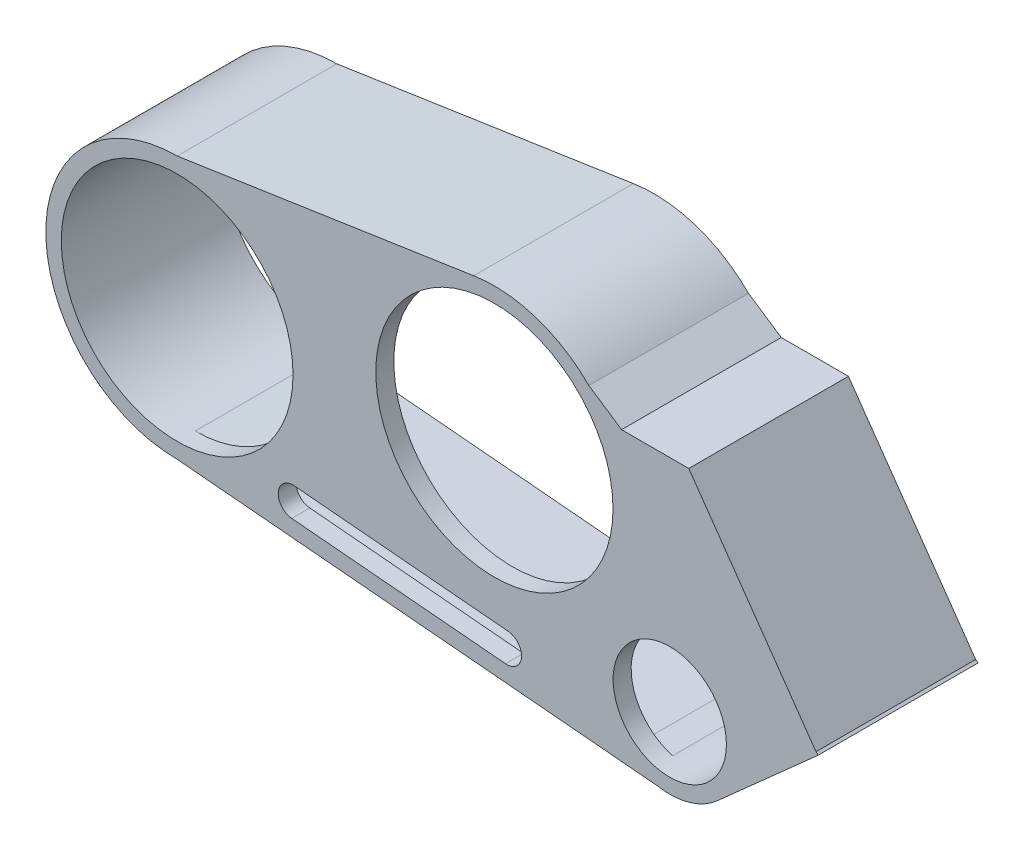
SolidWorks part; units mm, degrees
ref_plane "Front Plane" through (0, 0, 0) normal (0, 0, 1) x (1, 0, 0)
ref_plane "Top Plane" through (0, 0, 0) normal (0, 1, 0) x (1, 0, 0)
ref_plane "Right Plane" through (0, 0, 0) normal (1, 0, 0) x (0, 0, -1)
sketch "Sketch1" plane through (0, 0, 0) normal (0, 0, 1) x (1, 0, 0)
  line L1 (0, 0) -> (300, 0)
  line L2 (0, 0) -> (0, -152)
  line L3 (0, -152) -> (300, -152)
  line L4 (300, 0) -> (300, -152)
  dimension "D1" = 300
  dimension "D2" = 152
extrude "Boss-Extrude1" add sketch "Sketch1" along normal blind 62 contours L2 L3 L4 L1
sketch "Sketch2" plane through (0, 0, 62) normal (0, 0, 1) x (1, 0, 0)
  line L0 (0, -76) -> (51, -76) construction
  line L1 (0, 0) -> (0, -152) construction
  line L2 (177.6509, -152) -> (177.6509, -124.15) construction
  line L3 (0, -152) -> (300, -152) construction
  line L4 (102, -76) -> (174.2, -76) construction
  line L5 (174.2, -76) -> (174.2, -59) construction
  line L8 (242.3, -144) -> (242.3, -152) construction
  line L9 (300, 0) -> (300, -152) construction
  line L10 (270, -116.3) -> (300, -116.3) construction
  line L11 (300, -102) -> (273.9, -102)
  line L15 (286.95, -102) -> (286.95, -152) construction
  line L16 (51, -25) -> (166.1635, -7.6956)
  line L17 (51, -127) -> (242.3, -144)
  line L18 (232.9558, -32.8647) -> (226.0001, -22.2388) construction
  line L19 (226.0001, -22.2388) -> (210.8789, -22.2388) construction
  line L20 (257.068, -22.874) -> (251.9461, -20.1525) construction
  line L21 (210.8789, -22.2388) -> (251.9461, -20.1525)
  line L22 (251.9461, -20.1525) -> (300, -102)
  line L23 (300, -102) -> (260.7242, -136.9843)
  arc A0 (51, -25) -> (51, -127) centre (51, -76) ccw
  arc A1 (210.8789, -22.2388) -> (166.1635, -7.6956) centre (174.2, -59) ccw
  arc A2 (237.4154, -143.5659) -> (260.7242, -136.9843) centre (242.3, -116.3) ccw
  point P11 (0, 0)
  point P15 (0, 0)
  point P21 (242.3, -148)
  point P34 (0, 0)
  line M6 (300, 0) -> (0, 0)
  line M7 (0, 0) -> (0, -152)
  line M8 (0, -152) -> (300, -152)
  line M9 (300, -152) -> (300, 0)
  dimension "D5" = 103.86
  dimension "D6" = 55.4
  dimension "D7" = 4
  dimension "D1" = 51
  dimension "D2" = 27.85
  dimension "D3" = 72.2
  dimension "D4" = 17
  dimension "D8" = 30
  dimension "D9" = 26.1
  dimension "D10" = 80.35
  dimension "D11" = 26.1
  dimension "D13" = 50
  dimension "D14" = 12.7
  dimension "D15" = 5.8
extrude "Cut-Extrude2" cut sketch "Sketch2" against normal through all contours A2 L17 A0 L23 M7 M8 M9 | A1 L21 L22 A0 L16 M9 M6 M7 | L17 A0 L16 A1 L21 L22 L23 A2 region at (12.697, -37.697, 62) region at (133.2143, -138.3117, 62)
sketch "Sketch4" plane through (0, 0, 62) normal (0, 0, 1) x (1, 0, 0)
  line L4 (210.8789, -22.2388) -> (223.5789, -30.7442)
  line L5 (223.5789, -30.7442) -> (249.6789, -30.7442)
  line L6 (249.6789, -30.7442) -> (299.0826, -101.3)
  line L7 (299.0826, -101.3) -> (272.9826, -101.3)
  line L8 (272.9826, -101.3) -> (223.5789, -30.7442)
  circle A0 centre (51, -76) radius 51
  circle A1 centre (174.2, -59) radius 51.93
  arc A2 (237.4154, -143.5659) -> (260.7242, -136.9843) centre (242.3, -116.3) ccw construction
  circle A3 centre (242.3, -116.3) radius 27.7
  point P12 (0, 0)
  point P14 (0, 0)
  dimension "D1" = 103.86
  dimension "D2" = 55.4
  dimension "D7" = 102
  dimension "D3" = 125
  dimension "D4" = 15
  dimension "D5" = 26.1
  dimension "D6" = 12.7
sketch "Sketch6" plane through (0, 0, 62) normal (0, 0, 1) x (1, 0, 0)
  line L0 (94.9334, -130.9042) -> (96.509, -113.174) construction
  line L1 (51, -127) -> (237.4154, -143.5659) construction
  line L2 (177.9334, -138.28) -> (179.509, -120.5499) construction
  line L3 (95.491, -124.6289) -> (178.491, -132.0047)
  line L4 (96.509, -113.174) -> (179.509, -120.5499)
  arc A0 (96.509, -113.174) -> (95.491, -124.6289) centre (96, -118.9015) ccw
  arc A1 (178.491, -132.0047) -> (179.509, -120.5499) centre (179, -126.2773) ccw
  circle A2 centre (51, -76) radius 51 construction
  dimension "D4" = 45
  dimension "D1" = 11.5
  dimension "D2" = 6.3
  dimension "D3" = 83
sketch "Sketch7" plane through (0, 0, 62) normal (0, 0, 1) x (1, 0, 0)
  circle A0 centre (51, -76) radius 45
  circle A1 centre (174.2, -59) radius 46.06
  circle A2 centre (242.3, -116.3) radius 22
  dimension "D1" = 90
  dimension "D2" = 92.12
  dimension "D3" = 44
extrude "Cut-Extrude4" cut sketch "Sketch7" against normal through all
extrude "Cut-Extrude6" cut sketch "Sketch6" against normal through all contours L3 A1 L4 A0
sketch "Sketch10" plane through (0, 0, 62) normal (0, 0, 1) x (1, 0, 0)
  line L0 (210.8789, -22.2388) -> (223.5789, -30.7442)
  line L1 (223.5789, -30.7442) -> (249.6789, -30.7442)
  line L2 (249.6789, -30.7442) -> (299.0826, -101.3)
  line L4 (251.9461, -20.1525) -> (210.8789, -22.2388)
  line L7 (251.9461, -20.1525) -> (300, -102)
  line L8 (300, -102) -> (299.0826, -101.3)
extrude "Cut-Extrude9" cut sketch "Sketch10" against normal through all
shell "Shell2" thickness 5 removed face at (200.102, -72.4605, 0)
sketch "Sketch12" plane through (0, 0, 0) normal (0, 0, -1) x (-1, 0, 0)
  line L0 (-64.8922, -27.9687) -> (-51, -31)
  line L1 (-66.9266, -123.3956) -> (-51, -121)
  line L2 (-268.3148, -123.5272) -> (-259.1272, -130.472)
  line L3 (-225.572, -137.4938) -> (-236.3987, -137.4938)
  line L4 (-186.4595, -134.018) -> (-87.2924, -125.2054)
  line L6 (-218.2635, -33.2021) -> (-200.6668, -21.3034)
  line L7 (-147.3306, -15.5816) -> (-168.085, -13.3477)
  line L8 (-179.9516, -115.5695) -> (-96.9516, -108.1937)
  arc A1 (-51, -31) -> (-51, -121) centre (-51, -76) ccw
  circle A2 centre (-51, -76) radius 45 construction
  arc A3 (-66.9266, -123.3956) -> (-64.8922, -27.9687) centre (-51, -76) cw
  circle A4 centre (-242.3, -116.3) radius 22 construction
  arc A5 (-268.3148, -123.5272) -> (-225.572, -137.4938) centre (-242.3, -116.3) cw
  arc A6 (-259.1272, -130.472) -> (-236.3987, -137.4938) centre (-242.3, -116.3) cw
  arc A7 (-179.9516, -115.5695) -> (-186.4595, -134.018) centre (-179, -126.2773) ccw
  arc A8 (-87.2924, -125.2054) -> (-96.9516, -108.1937) centre (-96, -118.9015) ccw
  circle A9 centre (-174.2, -59) radius 46.06 construction
  arc A10 (-168.085, -13.3477) -> (-200.6668, -21.3034) centre (-174.2, -59) cw
  arc A11 (-218.2635, -33.2021) -> (-147.3306, -15.5816) centre (-174.2, -59) ccw
extrude "Cut-Extrude10" cut sketch "Sketch12" against normal blind 55
